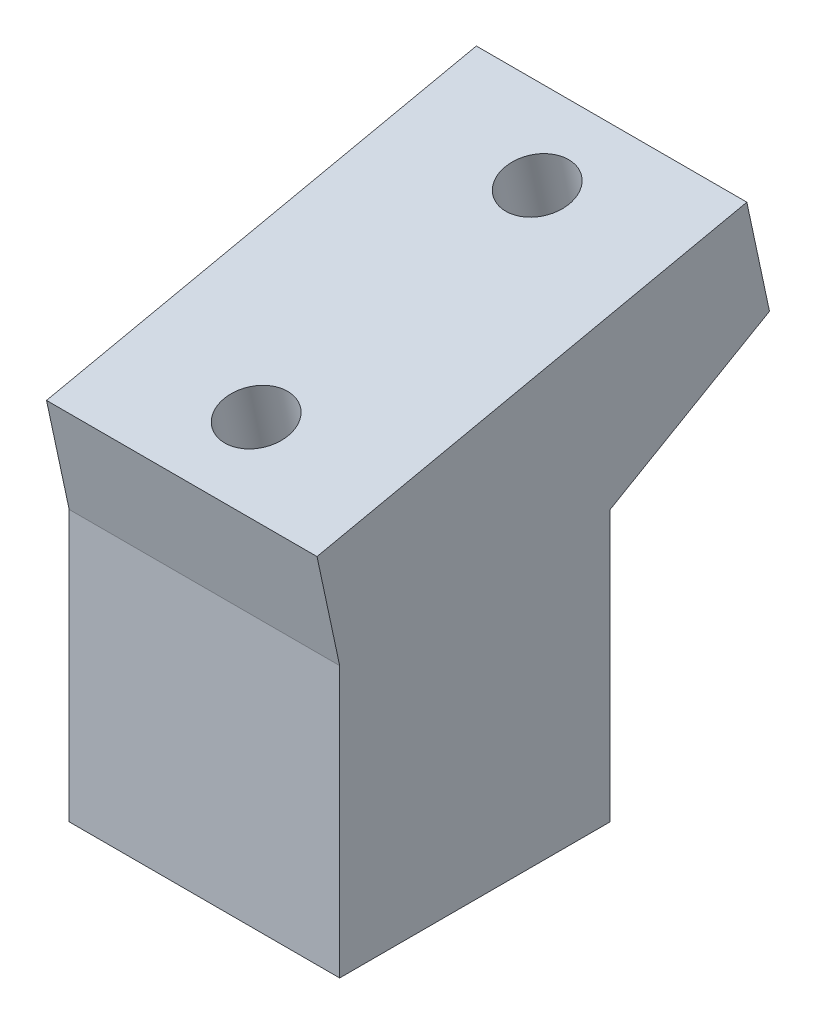
SolidWorks part; units mm, degrees
ref_plane "前视基准面" through (0, 0, 0) normal (0, 0, 1) x (1, 0, 0)
ref_plane "上视基准面" through (0, 0, 0) normal (0, 1, 0) x (1, 0, 0)
ref_plane "右视基准面" through (0, 0, 0) normal (1, 0, 0) x (0, 0, -1)
sketch "草图1" plane through (0, 0, 0) normal (0, 1, 0) x (1, 0, 0)
  line L1 (0, 0) -> (8, 0)
  line L2 (0, 0) -> (0, 8)
  line L3 (0, 8) -> (8, 8)
  line L4 (8, 0) -> (8, 8)
  line L5 (2.475, 2.475) -> (5.525, 2.475)
  line L6 (2.475, 2.475) -> (2.475, 5.525)
  line L7 (2.475, 5.525) -> (5.525, 5.525)
  line L8 (5.525, 2.475) -> (5.525, 5.525)
  point P9 (4, 2.475)
  point P10 (4, 0)
  point P11 (0, 4)
  point P12 (2.475, 4)
  dimension "D1" = 8
  dimension "D2" = 8
  dimension "D3" = 3.05
  dimension "D4" = 3.05
extrude "凸台-拉伸1" add sketch "草图1" along normal blind 7.5
sketch "草图2" plane through (0, 7.5, 0) normal (0, 1, 0) x (1, 0, 0)
  line L4 (0, 8) -> (0, 0)
  line L5 (0, 0) -> (8, 0)
  line L6 (8, 0) -> (8, 8)
  line L7 (8, 8) -> (0, 8)
  line L8 (0, 8) -> (0, 0)
  line L9 (0, 0) -> (8, 0)
  line L10 (8, 0) -> (8, 8)
  line L11 (8, 8) -> (0, 8)
  dimension "D1" = 0
extrude "凸台-拉伸2" add sketch "草图2" along normal blind 0.5
sketch "草图3" plane through (8, 0, 0) normal (1, 0, 0) x (0, 0, -1)
  line L0 (8, 8) -> (12.7121, 10.7206)
  line L1 (12.7121, 10.7206) -> (0, 8)
  line L2 (0, 8) -> (-0.6697, 11.1291)
  line L3 (-0.6697, 11.1291) -> (12.0425, 13.8497)
  line L4 (12.0425, 13.8497) -> (12.7121, 10.7206)
  line L5 (8, 8) -> (8, 0) construction
  line M8 (8, 8) -> (0, 8)
  dimension "D1" = 120
  dimension "D2" = 13
  dimension "D3" = 3.2
extrude "凸台-拉伸3" add sketch "草图3" against normal up to surface (8 mm away) contours L4 L3 L2 L1 | L0 L1 M8 region at (8, 8.9069, -6.904) region at (8, 10.9248, -6.0212) up to face at (0, 4, -4)
sketch "草图4" plane through (0, 10.7788, 2.3068) normal (0, 0.9779, 0.2093) x (1, 0, 0)
  line L0 (4, 1.6742) -> (4, 14.6742) construction
  line L1 (0, 1.6742) -> (8, 1.6742) construction
  line L2 (0, 14.6742) -> (8, 14.6742) construction
  line L3 (8, 8.1742) -> (0, 8.1742) construction
  line L4 (8, 1.6742) -> (8, 14.6742) construction
  line L5 (0, 14.6742) -> (0, 1.6742) construction
  circle A0 centre (4, 3.9242) radius 0.95
  circle A1 centre (4, 12.4242) radius 0.95
  dimension "D1" = 1.9
  dimension "D2" = 8.5
extrude "凸台-拉伸4" add sketch "草图4" against normal blind 4
extrude "切除-拉伸1" cut sketch "草图4<2>" against normal blind 4.2
sketch "草图4<2>" plane through (0, 10.7788, 2.3068) normal (0, 0.9779, 0.2093) x (1, 0, 0) same geometry as "草图4"
